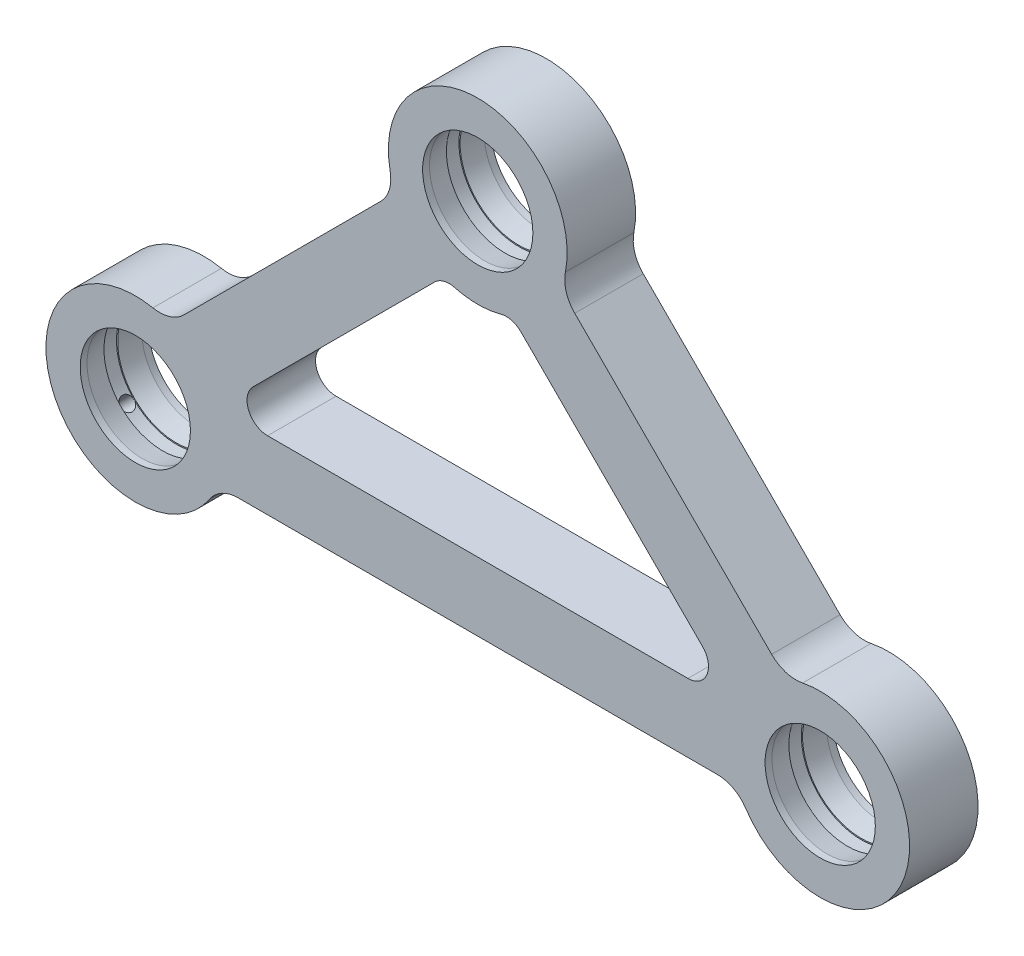
SolidWorks part; units mm, degrees
ref_plane "Front Plane" through (0, 0, 0) normal (0, 0, 1) x (1, 0, 0)
ref_plane "Top Plane" through (0, 0, 0) normal (0, 1, 0) x (1, 0, 0)
ref_plane "Right Plane" through (0, 0, 0) normal (1, 0, 0) x (0, 0, -1)
sketch "Sketch1" plane through (0, 0, 0) normal (0, 0, 1) x (1, 0, 0)
  line L0 (-26.538, 0) -> (73.462, 0) construction
  line L2 (-26.538, 0) -> (23.462, 50) construction
  line L3 (23.462, 50) -> (73.462, 0) construction
  line L4 (-14.4839, 5) -> (61.4078, 5)
  line L5 (-14.4839, -5) -> (61.4078, -5)
  line L6 (-21.55, 12.0591) -> (11.4029, 45.012)
  line L7 (18.474, 37.9409) -> (-14.4789, 4.988)
  line L8 (28.45, 37.9409) -> (61.4029, 4.988)
  line L9 (35.5211, 45.012) -> (68.474, 12.0591)
  circle A0 centre (23.462, 50) radius 8.05
  circle A1 centre (73.462, 0) radius 8.05
  circle A2 centre (-26.538, 0) radius 8.05
  circle A3 centre (-26.538, 0) radius 13.05
  circle A4 centre (23.462, 50) radius 13.05
  circle A5 centre (73.462, 0) radius 13.05
  dimension "D1" = 16.1
  dimension "D2" = 16.1
  dimension "D3" = 16.1
  dimension "D4" = 45
  dimension "D5" = 45
  dimension "D6" = 100
  dimension "D7" = 5
  dimension "D8" = 5
  dimension "D9" = 5
  dimension "D10" = 5
  dimension "D11" = 5
  dimension "D12" = 5
  dimension "D13" = 5
  dimension "D14" = 5
  dimension "D15" = 5
extrude "Boss-Extrude1" add sketch "Sketch1" along normal blind 8 contours A3 A2 | A4 L6 A3 L4 L7 | A4 A0 | A5 L9 A4 L8 L4 | A5 L8 L4 L7 A3 L5 | A5 A1 | A3 L7 L4 | A5 L4 L8 region at (-1.538, 25, 0) region at (-14.4766, 4.996, 0) region at (-14.8224, 4.8528, 0) region at (23.462, 0, 0) region at (48.462, 25, 0) region at (61.4006, 4.996, 0) region at (14.4953, 41.0333, 0) region at (64.4997, 8.9712, 0)
sketch3d "3DSketch1" plane through (0, 0, 0) normal (0, 0, 1) x (1, 0, 0)
  dimension "D1" = 4
sketch "Sketch3" plane through (0, 0, 4) normal (0, 0, 1) x (1, 0, 0)
  circle A0 centre (-26.538, 0) radius 8.7553
  circle A1 centre (23.462, 50) radius 8.7553
  circle A2 centre (73.462, 0) radius 8.7553
  circle A3 centre (-26.538, 0) radius 8.05 construction
  circle A4 centre (23.462, 50) radius 8.05 construction
  circle A5 centre (73.462, 0) radius 8.05 construction
  dimension "D1" = 0.7053
  dimension "D2" = 0.7053
  dimension "D3" = 0.7053
extrude "Cut-Extrude1" cut sketch "Sketch3" against normal blind 1 and the other way blind 1 contours A1 | A0 | A2
sketch3d "3DSketch2" plane through (0, 0, 0) normal (0, 0, 1) x (1, 0, 0)
sketch3d "3DSketch3" plane through (0, 0, 0) normal (0, 0, 1) x (1, 0, 0)
  dimension "D1" = 26
sketch "Sketch4" plane through (0, 62.95, 0) normal (0, -1, 0) x (-1, 0, 0)
  line L0 (-41.8, -4) -> (41.8, -4) construction
  line L1 (-86.512, 0) -> (-86.512, -8) construction
  line L4 (-36.5118, -8) -> (-68.474, -8)
  line L5 (-36.5118, -8) -> (-68.474, -8)
  line L6 (-68.474, -8) -> (-86.512, -8)
  line L7 (-68.474, -8) -> (-86.512, -8)
  line L8 (-86.512, -8) -> (-86.512, 0)
  line L9 (-86.512, -8) -> (-86.512, 0)
  line L10 (-86.512, 0) -> (-68.474, 0)
  line L11 (-86.512, 0) -> (-68.474, 0)
  line L12 (-68.474, 0) -> (-36.5118, 0)
  line L13 (-68.474, 0) -> (-36.5118, 0)
  line L14 (-36.5118, 0) -> (-10.4122, 0)
  line L15 (-36.5118, 0) -> (-10.4122, 0)
  line L16 (-10.4122, 0) -> (21.55, 0)
  line L17 (-10.4122, 0) -> (21.55, 0)
  line L18 (21.55, 0) -> (39.588, 0)
  line L19 (21.55, 0) -> (39.588, 0)
  line L20 (39.588, 0) -> (39.588, -8)
  line L21 (39.588, 0) -> (39.588, -8)
  line L22 (39.588, -8) -> (21.55, -8)
  line L23 (39.588, -8) -> (21.55, -8)
  line L24 (21.55, -8) -> (-10.4122, -8)
  line L25 (21.55, -8) -> (-10.4122, -8)
  line L26 (-10.4122, -8) -> (-36.5118, -8)
  line L27 (-10.4122, -8) -> (-36.5118, -8)
  circle A0 centre (-23.462, -4) radius 1
  dimension "D1" = 2
  dimension "D2" = 63.05
  dimension "D3" = 126.1
extrude "Cut-Extrude2" cut sketch "Sketch4" along normal blind 6 contours A0
fillet "Fillet1" radius 3 4 edges at (-14.4669, 5, 4) (18.474, 37.9409, 4) (28.45, 37.9409, 4) (61.3909, 5, 4)
fillet "Fillet2" radius 5 6 edges at (68.474, 12.0591, 4) (35.5211, 45.012, 4) (11.4029, 45.012, 4) (-21.55, 12.0591, 4) (-14.4839, -5, 4) (61.4078, -5, 4)
sketch3d "3DSketch4" plane through (0, 0, 0) normal (0, 0, 1) x (1, 0, 0)
sketch3d "3DSketch5" plane through (0, 0, 0) normal (0, 0, 1) x (1, 0, 0)
  dimension "D1" = 26
sketch "Sketch5" plane through (45.888, -45.888, 0) normal (-0.7071, 0.7071, 0) x (0, 0, 1)
  line L0 (8, -31.8152) -> (8, -7.901) construction
  line L1 (8, 43.8955) -> (8, 59.9955) construction
  line L2 (8, 43.8955) -> (8, 59.9955)
  line L7 (8, 64.9955) -> (0, 64.9955) construction
  line L8 (8, 64.9955) -> (0, 64.9955)
  circle A0 centre (4, 51.9455) radius 1
  dimension "D1" = 2
  dimension "D2" = 4
  dimension "D3" = 8.05
  dimension "D4" = 16.1
extrude "Cut-Extrude3" cut sketch "Sketch5" along normal blind 10 contours A0 region at (82.619, -9.157, 4)
draft "Draft4" type of draft neutral plane draft angle 10 faces to draft 3 face at (-18.488, 0, 5) face at (31.512, 50, 5) face at (81.512, 0, 5) neutral plane through (0, 0, 8) neutral plane normal (0, 0, 1) reverse direction yes parameters "D1"=10
draft "Draft6" type of draft neutral plane draft angle 10 faces to draft 3 face at (-18.488, 0, 0) face at (81.512, 0, 0) face at (31.512, 50, 0) neutral plane through (0, 0, 0) neutral plane normal (0, 0, -1) reverse direction yes parameters "D1"=10
sketch3d "3DSketch6" plane through (0, 0, 0) normal (0, 0, 1) x (1, 0, 0)
sketch3d "3DSketch8" plane through (0, 0, 0) normal (0, 0, 1) x (1, 0, 0)
  dimension "D1" = 26
sketch "Sketch6" plane through (-22.426, -22.426, 0) normal (0.7071, 0.7071, 0) x (0, 0, -1)
  line L0 (-8, 31.8152) -> (-8, 5.7152) construction
  line L1 (0, 31.8152) -> (-8, 31.8152) construction
  line L2 (0, 31.8152) -> (-8, 31.8152)
  line L3 (0, 10.7152) -> (0, 26.8152) construction
  line L4 (0, 10.7152) -> (0, 26.8152)
  circle A0 centre (-4, 18.7652) radius 1
  dimension "D1" = 2
  dimension "D2" = 4
  dimension "D4" = 16.1
  dimension "D5" = 8.05
extrude "Cut-Extrude4" cut sketch "Sketch6" along normal blind 10 contours A0
sketch "Sketch7" plane through (0, 0, 8) normal (0, 0, 1) x (1, 0, 0)
  line L2 (-7.2243, 5) -> (54.1483, 5) construction
  line L5 (17.1588, 36.6257) -> (-9.3456, 10.1213) construction
  line L10 (29.7652, 36.6257) -> (56.2696, 10.1213) construction
  line L11 (66.372, 14.161) -> (37.623, 42.91)
  line L12 (9.301, 42.91) -> (-19.448, 14.161)
  line L13 (-11.5113, -5) -> (58.4353, -5)
  line L14 (66.372, 14.161) -> (37.623, 42.91)
  line L15 (9.301, 42.91) -> (-19.448, 14.161)
  line L16 (-11.5113, -5) -> (58.4353, -5)
  line L17 (-7.2243, 5) -> (54.1483, 5)
  line L18 (17.1588, 36.6257) -> (-9.3456, 10.1213)
  line L19 (29.7652, 36.6257) -> (56.2696, 10.1213)
  circle A36 centre (-26.538, 0) radius 8.05 construction
  arc A37 (-9.3456, 10.1213) -> (-7.2243, 5) centre (-7.2243, 8) ccw construction
  arc A38 (54.1483, 5) -> (56.2696, 10.1213) centre (54.1483, 8) ccw construction
  circle A39 centre (73.462, 0) radius 8.05 construction
  circle A40 centre (23.462, 50) radius 8.05 construction
  arc A41 (29.7652, 36.6257) -> (26.8622, 37.4008) centre (27.6439, 34.5044) ccw construction
  arc A42 (20.0618, 37.4008) -> (26.8622, 37.4008) centre (23.462, 50) ccw construction
  arc A43 (20.0618, 37.4008) -> (17.1588, 36.6257) centre (19.2801, 34.5044) ccw construction
  circle A44 centre (-26.538, 0) radius 8.05
  arc A45 (36.2565, 47.4302) -> (37.623, 42.91) centre (41.1586, 46.4456) ccw
  arc A46 (36.2565, 47.4302) -> (10.6675, 47.4302) centre (23.462, 50) ccw
  arc A47 (9.301, 42.91) -> (10.6675, 47.4302) centre (5.7654, 46.4456) ccw
  arc A48 (-23.9682, 12.7945) -> (-19.448, 14.161) centre (-22.9836, 17.6966) ccw
  arc A49 (-23.9682, 12.7945) -> (-15.6738, -7.2299) centre (-26.538, 0) ccw
  arc A50 (-11.5113, -5) -> (-15.6738, -7.2299) centre (-11.5113, -10) ccw
  arc A51 (62.5978, -7.2299) -> (58.4353, -5) centre (58.4353, -10) ccw
  arc A52 (62.5978, -7.2299) -> (70.8922, 12.7945) centre (73.462, 0) ccw
  arc A53 (66.372, 14.161) -> (70.8922, 12.7945) centre (69.9076, 17.6966) ccw
  arc A54 (36.2565, 47.4302) -> (37.623, 42.91) centre (41.1586, 46.4456) ccw
  arc A55 (36.2565, 47.4302) -> (10.6675, 47.4302) centre (23.462, 50) ccw
  arc A56 (9.301, 42.91) -> (10.6675, 47.4302) centre (5.7654, 46.4456) ccw
  arc A57 (-23.9682, 12.7945) -> (-19.448, 14.161) centre (-22.9836, 17.6966) ccw
  arc A58 (-23.9682, 12.7945) -> (-15.6738, -7.2299) centre (-26.538, 0) ccw
  arc A59 (-11.5113, -5) -> (-15.6738, -7.2299) centre (-11.5113, -10) ccw
  arc A60 (62.5978, -7.2299) -> (58.4353, -5) centre (58.4353, -10) ccw
  arc A61 (62.5978, -7.2299) -> (70.8922, 12.7945) centre (73.462, 0) ccw
  arc A62 (66.372, 14.161) -> (70.8922, 12.7945) centre (69.9076, 17.6966) ccw
  arc A63 (-9.3456, 10.1213) -> (-7.2243, 5) centre (-7.2243, 8) ccw
  arc A64 (54.1483, 5) -> (56.2696, 10.1213) centre (54.1483, 8) ccw
  circle A65 centre (73.462, 0) radius 8.05
  circle A66 centre (23.462, 50) radius 8.05
  arc A67 (29.7652, 36.6257) -> (26.8622, 37.4008) centre (27.6439, 34.5044) ccw
  arc A68 (20.0618, 37.4008) -> (26.8622, 37.4008) centre (23.462, 50) ccw
  arc A69 (20.0618, 37.4008) -> (17.1588, 36.6257) centre (19.2801, 34.5044) ccw
  dimension "D1" = 0
extrude "Boss-Extrude3" add sketch "Sketch7" along normal blind 1
sketch "Sketch11" plane through (0, 0, 0) normal (0, 0, -1) x (-1, 0, 0)
  line L0 (-29.7652, 36.6257) -> (-56.2696, 10.1213) construction
  line L1 (7.2243, 5) -> (-54.1483, 5) construction
  line L2 (-17.1588, 36.6257) -> (9.3456, 10.1213) construction
  line L3 (-37.623, 42.91) -> (-66.372, 14.161)
  line L4 (-58.4353, -5) -> (11.5113, -5)
  line L5 (19.448, 14.161) -> (-9.301, 42.91)
  line L6 (-37.623, 42.91) -> (-66.372, 14.161)
  line L7 (-58.4353, -5) -> (11.5113, -5)
  line L8 (19.448, 14.161) -> (-9.301, 42.91)
  line L9 (-17.1588, 36.6257) -> (9.3456, 10.1213)
  line L10 (7.2243, 5) -> (-54.1483, 5)
  line L11 (-29.7652, 36.6257) -> (-56.2696, 10.1213)
  circle A0 centre (-23.462, 50) radius 8.05 construction
  circle A1 centre (-73.462, 0) radius 8.05
  circle A2 centre (-73.462, 0) radius 8.05
  circle A3 centre (-23.462, 50) radius 8.05
  circle A4 centre (26.538, 0) radius 8.05 construction
  circle A5 centre (26.538, 0) radius 8.05
  arc A6 (-17.1588, 36.6257) -> (-20.0618, 37.4008) centre (-19.2801, 34.5044) ccw construction
  arc A7 (-26.8622, 37.4008) -> (-20.0618, 37.4008) centre (-23.462, 50) ccw construction
  arc A8 (-26.8622, 37.4008) -> (-29.7652, 36.6257) centre (-27.6439, 34.5044) ccw construction
  arc A9 (-56.2696, 10.1213) -> (-54.1483, 5) centre (-54.1483, 8) ccw construction
  arc A10 (7.2243, 5) -> (9.3456, 10.1213) centre (7.2243, 8) ccw construction
  arc A11 (-10.6675, 47.4302) -> (-36.2565, 47.4302) centre (-23.462, 50) ccw
  arc A12 (-37.623, 42.91) -> (-36.2565, 47.4302) centre (-41.1586, 46.4456) ccw
  arc A13 (-70.8922, 12.7945) -> (-66.372, 14.161) centre (-69.9076, 17.6966) ccw
  arc A14 (-70.8922, 12.7945) -> (-62.5978, -7.2299) centre (-73.462, 0) ccw
  arc A15 (-58.4353, -5) -> (-62.5978, -7.2299) centre (-58.4353, -10) ccw
  arc A16 (15.6738, -7.2299) -> (11.5113, -5) centre (11.5113, -10) ccw
  arc A17 (15.6738, -7.2299) -> (23.9682, 12.7945) centre (26.538, 0) ccw
  arc A18 (19.448, 14.161) -> (23.9682, 12.7945) centre (22.9836, 17.6966) ccw
  arc A19 (-10.6675, 47.4302) -> (-9.301, 42.91) centre (-5.7654, 46.4456) ccw
  arc A20 (-10.6675, 47.4302) -> (-36.2565, 47.4302) centre (-23.462, 50) ccw
  arc A21 (-37.623, 42.91) -> (-36.2565, 47.4302) centre (-41.1586, 46.4456) ccw
  arc A22 (-70.8922, 12.7945) -> (-66.372, 14.161) centre (-69.9076, 17.6966) ccw
  arc A23 (-70.8922, 12.7945) -> (-62.5978, -7.2299) centre (-73.462, 0) ccw
  arc A24 (-58.4353, -5) -> (-62.5978, -7.2299) centre (-58.4353, -10) ccw
  arc A25 (15.6738, -7.2299) -> (11.5113, -5) centre (11.5113, -10) ccw
  arc A26 (15.6738, -7.2299) -> (23.9682, 12.7945) centre (26.538, 0) ccw
  arc A27 (19.448, 14.161) -> (23.9682, 12.7945) centre (22.9836, 17.6966) ccw
  arc A28 (-10.6675, 47.4302) -> (-9.301, 42.91) centre (-5.7654, 46.4456) ccw
  arc A29 (7.2243, 5) -> (9.3456, 10.1213) centre (7.2243, 8) ccw
  arc A30 (-56.2696, 10.1213) -> (-54.1483, 5) centre (-54.1483, 8) ccw
  arc A31 (-26.8622, 37.4008) -> (-29.7652, 36.6257) centre (-27.6439, 34.5044) ccw
  arc A32 (-26.8622, 37.4008) -> (-20.0618, 37.4008) centre (-23.462, 50) ccw
  arc A33 (-17.1588, 36.6257) -> (-20.0618, 37.4008) centre (-19.2801, 34.5044) ccw
  dimension "D1" = 0
  dimension "D2" = 0
extrude "Boss-Extrude4" add sketch "Sketch11" along normal blind 1
equation "\"D2@Sketch1\"=\"D1@Sketch1\""
equation "\"D3@Sketch1\"=\"D1@Sketch1\""
equation "\"D5@Sketch1\"=\"D4@Sketch1\""
equation "\"D8@Sketch1\"=\"D7@Sketch1\""
equation "\"D9@Sketch1\"=\"D7@Sketch1\""
equation "\"D11@Sketch1\"=\"D10@Sketch1\""
equation "\"D12@Sketch1\"=\"D10@Sketch1\""
equation "\"D13@Sketch1\"=\"D10@Sketch1\""
equation "\"D14@Sketch1\"=\"D13@Sketch1\""
equation "\"D15@Sketch1\"=\"D14@Sketch1\""
equation "\"D2@Sketch3\"=\"D1@Sketch3\""
equation "\"D3@Sketch3\"=\"D1@Sketch3\""
equation "\"D2@Sketch4\"=\"D3@Sketch4\"/2"
equation "\"D3@Sketch5\"=\"D4@Sketch5\"/2"
equation "\"D2@Sketch5\"=\"D5@Sketch5\"/2"
equation "\"D2@Sketch6\"=\"D3@Sketch6\"/2"
equation "\"D5@Sketch6\"=\"D4@Sketch6\"/2"
equation "\"D1@Sketch3\"=4*tan(10)"
